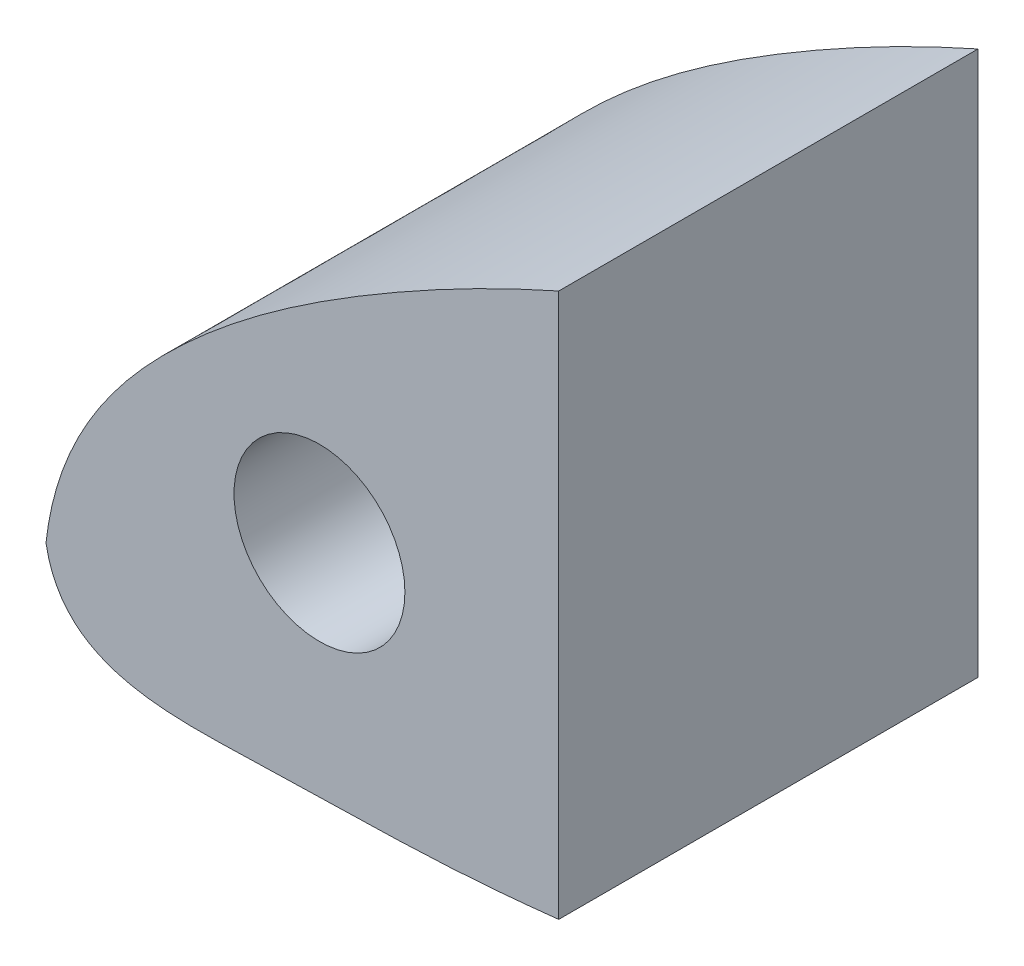
SolidWorks part; units mm, degrees
ref_plane "Front Plane" through (0, 0, 0) normal (0, 0, 1) x (1, 0, 0)
ref_plane "Top Plane" through (0, 0, 0) normal (0, 1, 0) x (1, 0, 0)
ref_plane "Right Plane" through (0, 0, 0) normal (1, 0, 0) x (0, 0, -1)
sketch "Sketch1" plane through (0, 0, 0) normal (0, 0, 1) x (1, 0, 0)
  spline S0 degree 3 poles (0.0006, 0.0001) (0.8106, 7.3592) (8.6491, 17.8566) (26.2867, 29.9752) (52.1111, 42.0692) (89.5976, 49.2908) (131.4008, 47.8848) (173.2567, 40.0411) (217.9611, 29.613) (256.9521, 19.5289) (290.3598, 8.711) (301.2732, 4.3828) (314.8169, -0.5162) (309.8463, 0.0001) knots 0 0 0 0 0.060864 0.113688 0.188609 0.312909 0.448482 0.557612 0.691544 0.852438 0.929756 0.976058 1 1 1 1
  spline S1 degree 3 poles (309.8463, 0.0001) (303.9568, 1.471) (293.9895, 2.094) (276.264, 4.5144) (260.8463, 5.4274) (235.8588, 7.8703) (205.1014, 8.8381) (157.7186, 9.0307) (110.4973, 6.1815) (66.5062, -0.5867) (36.4547, -6.0985) (15.3166, -6.1891) (1.2307, -6.9241) (0.0006, 0.0001) knots 0 0 0 0 0.057787 0.095275 0.171021 0.205339 0.335319 0.464904 0.658702 0.785512 0.893517 0.943092 1 1 1 1
extrude "Boss-Extrude1" add sketch "Sketch1" along normal blind 31.1531
sketch "Sketch2" plane through (0, 0, 31.1531) normal (0, 0, 1) x (1, 0, 0)
  circle A0 centre (20.32, 10.16) radius 6.35
  circle A1 centre (227.2963, 19.0501) radius 3.175
  dimension "D2" = 12.7
  dimension "D3" = 6.35
  dimension "D6" = 20.32
  dimension "D1" = 82.55
  dimension "D4" = 19.05
  dimension "D5" = 10.16
extrude "Cut-Extrude1" cut sketch "Sketch2" against normal through all
sketch "Sketch3" plane through (0, 0, 31.1531) normal (0, 0, 1) x (1, 0, 0)
  line L1 (38.1, 71.718) -> (331.2889, 71.718)
  line L2 (38.1, 71.718) -> (38.1, -66.2532)
  line L3 (38.1, -66.2532) -> (331.2889, -66.2532)
  line L4 (331.2889, 71.718) -> (331.2889, -66.2532)
  dimension "D1" = 38.1
extrude "Cut-Extrude2" cut sketch "Sketch3" against normal through all
